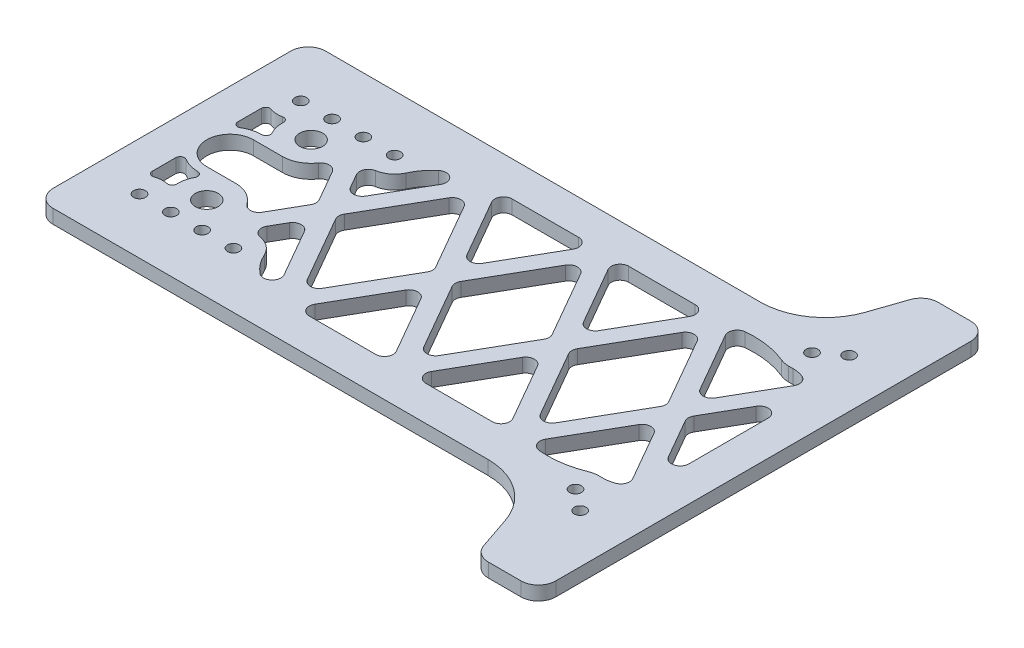
SolidWorks part; units mm, degrees
ref_plane "Front Plane" through (0, 0, 0) normal (0, 0, 1) x (1, 0, 0)
ref_plane "Top Plane" through (0, 0, 0) normal (0, 1, 0) x (1, 0, 0)
ref_plane "Right Plane" through (0, 0, 0) normal (1, 0, 0) x (0, 0, -1)
sketch "Sketch2" plane through (0, 0, 0) normal (0, 1, 0) x (1, 0, 0)
  line L1 (-85, -74.5) -> (85, -74.5)
  line L2 (-85, -74.5) -> (-85, 74.5)
  line L3 (-85, 74.5) -> (85, 74.5)
  line L4 (85, -74.5) -> (85, 74.5)
  line L5 (-85, -74.5) -> (85, 74.5) construction
  line L6 (-85, 74.5) -> (85, -74.5) construction
  point P0 (0, 0)
  dimension "D1" = 149
  dimension "D2" = 170
extrude "Boss-Extrude1" add sketch "Sketch2" along normal blind 4
hole_wizard "M3 Clearance Hole1" positions "Sketch7" profile "Sketch8" hole size "M3" standard "ANSI Metric" end condition through all
sketch "Sketch7" plane through (0, 4, 0) normal (0, 1, 0) x (1, 0, 0)
  line L0 (-85, 74.5) -> (-85, -74.5) construction
  line L1 (-85, -74.5) -> (85, -74.5) construction
  line L2 (85, -74.5) -> (85, 74.5) construction
  point P0 (-71.16, -23.18)
  point P2 (-62.16, -23.18)
  point P4 (-53.16, -23.18)
  point P6 (-44.16, -23.18)
  point P8 (71, -38.66)
  point P10 (65, -34)
  dimension "D1" = 13.84
  dimension "D2" = 51.32
  dimension "D3" = 9
  dimension "D4" = 51.32
  dimension "D5" = 9
  dimension "D6" = 51.32
  dimension "D7" = 9
  dimension "D8" = 51.32
  dimension "D9" = 40.5
  dimension "D10" = 20
  dimension "D11" = 35.84
  dimension "D12" = 14
sketch "Sketch8" plane through (-71.16, 4, 23.18) normal (1, 0, 0) x (0, 0, 1)
  line L0 (0, 0) -> (0, 4)
  line L1 (0, 4) -> (1.7, 4)
  line L2 (1.7, 4) -> (1.7, 0)
  line L5 (1.7, 0) -> (0, 0)
  line L11 (0, -6.35) -> (0, 107.95) construction
  dimension "Thru Hole Dia." = 3.4
  dimension "Thru Hole Depth" = 4
sketch "Sketch9" plane through (0, 4, 0) normal (0, 1, 0) x (1, 0, 0)
  line L0 (-85, 0) -> (85, 0) construction
  line L1 (-85, 74.5) -> (-85, -74.5) construction
  line L2 (85, -74.5) -> (85, 74.5) construction
mirror "Mirror1" about plane through (0, 0, 0) normal (0, 0, 1) of "M3 Clearance Hole1"
sketch "Sketch10" [suppressed] plane through (0, 10, 0) normal (0, 1, 0) x (1, 0, 0)
  line L0 (-85, 74.5) -> (-85, -74.5) construction
  line L1 (-85, -39.5) -> (45.3, -39.5)
  line L2 (-85, -39.5) -> (-85, -74.5)
  line L3 (-85, -74.5) -> (45.3, -74.5)
  line L4 (45.3, -39.5) -> (45.3, -74.5)
  line L5 (-85, -74.5) -> (85, -74.5) construction
  dimension "D1" = 130.3
  dimension "D2" = 35
extrude "Cut-Extrude1" [suppressed] cut sketch "Sketch10" against normal blind 10
sketch "Sketch11" [suppressed] plane through (0, 10, 0) normal (0, 1, 0) x (1, 0, 0)
  line L0 (45.3, -39.5) -> (85, -74.5)
  line L1 (85, -74.5) -> (45.3, -74.5)
  line L2 (45.3, -74.5) -> (45.3, -39.5)
extrude "Cut-Extrude2" [suppressed] cut sketch "Sketch11" against normal blind 10
sketch "Sketch12" plane through (0, 0, 0) normal (0, 1, 0) x (1, 0, 0)
  line L0 (-85, 39.1609) -> (45, 39.1609)
  line L1 (62.6547, 51.8097) -> (67.0194, 64.6606)
  line L2 (67.0194, 64.6606) -> (85, 64.6606)
  line L3 (85, 64.6606) -> (85, 0)
  line L4 (85, -74.5) -> (85, 74.5)
  line L5 (85, 74.5) -> (-85, 74.5)
  line L6 (-85, 74.5) -> (-85, -74.5)
  line L7 (-85, -74.5) -> (85, -74.5)
  line L8 (85, -74.5) -> (85, 74.5)
  line L9 (85, 74.5) -> (-85, 74.5)
  line L10 (-85, 74.5) -> (-85, -74.5)
  line L11 (-85, -74.5) -> (85, -74.5)
  line L12 (-2.2, 0) -> (2.2, 0) construction
  line L13 (67.0194, -64.6606) -> (85, -64.6606)
  line L14 (62.6547, -51.8097) -> (67.0194, -64.6606)
  line L15 (-85, -39.1609) -> (45, -39.1609)
  arc A0 (45, 39.1609) -> (62.6547, 51.8097) centre (45, 57.8061) ccw
  arc A1 (45, -39.1609) -> (62.6547, -51.8097) centre (45, -57.8061) cw
  dimension "D2" = 130
  dimension "D1" = 0
extrude "Cut-Extrude4" cut sketch "Sketch12" against normal through all and the other way through all contours L0 A0 L1 L2 L8 L9 L10 | A1 L15 L10 L11 L8 L13 L14 region at (-8.1008, 0, -57.5262) region at (-8.1008, 0, 57.5262)
hole_wizard "M6 Clearance Hole1" positions "Sketch13" profile "Sketch14" hole size "M6" standard "ANSI Metric" end condition through all
sketch "Sketch13" plane through (0, 4, 0) normal (0, 1, 0) x (1, 0, 0)
  line L0 (-85, 0) -> (85, 0) construction
  line L1 (-2.2, 0) -> (2.2, 0) construction
  line L2 (-85, 39.1609) -> (-85, -39.1609) construction
  point P0 (-60, -15)
  point P8 (-60, 15)
  dimension "D1" = 15
  dimension "D2" = 25
sketch "Sketch14" plane through (-60, 4, 15) normal (1, 0, 0) x (0, 0, 1)
  line L0 (0, 0) -> (0, 4)
  line L1 (0, 4) -> (3.3, 4)
  line L2 (3.3, 4) -> (3.3, 0)
  line L5 (3.3, 0) -> (0, 0)
  line L11 (0, -6.35) -> (0, 107.95) construction
  dimension "Thru Hole Dia." = 6.6
  dimension "Thru Hole Depth" = 4
fillet "Fillet1" radius 5 6 edges at (67.0194, 2, -64.6606) (85, 2, -64.6606) (85, 2, 64.6606) (67.0194, 2, 64.6606) (-85, 2, 39.1609) (-85, 2, -39.1609)
sketch "Sketch15" plane through (0, 4, 0) normal (0, 1, 0) x (1, 0, 0)
  line L0 (65, -27.3) -> (66.2406, -27.3)
  line L1 (-50.31, 17.4014) -> (-23.5629, -29.1609)
  line L2 (-50.31, -17.4014) -> (-23.5629, 29.1609)
  line L3 (-23.5629, -29.1609) -> (9.9394, 29.1609)
  line L4 (9.9394, 29.1609) -> (43.4416, -29.1609)
  line L5 (43.4416, -29.1609) -> (73.5852, 23.3139)
  line L6 (-23.5629, 29.1609) -> (9.9394, -29.1609)
  line L7 (9.9394, -29.1609) -> (43.4416, 29.1609)
  line L8 (43.4416, 29.1609) -> (73.5852, -23.3139)
  line L9 (-2.2, 0) -> (2.2, 0) construction
  line L10 (-60, 6.7) -> (-68.3, 6.7)
  line L11 (-68.3, -6.7) -> (-60, -6.7)
  line L12 (65, 27.3) -> (66.2406, 27.3)
  line L13 (-48.1422, -18.6467) -> (-23.5629, 24.1419)
  line L14 (-23.5629, 24.1419) -> (9.9394, -34.1799)
  line L15 (9.9394, -34.1799) -> (43.4416, 24.1419)
  line L16 (75, 54.6606) -> (74.184, 54.6606)
  line L17 (74.184, 54.6606) -> (72.1234, 48.5937)
  line L18 (45, 29.1609) -> (-75, 29.1609)
  line L19 (-75, 29.1609) -> (-75, -29.1609)
  line L20 (-75, -29.1609) -> (45, -29.1609)
  line L21 (72.1234, -48.5937) -> (74.184, -54.6606)
  line L22 (74.184, -54.6606) -> (75, -54.6606)
  line L23 (75, -54.6606) -> (75, 54.6606)
  line L24 (75, 54.6606) -> (74.184, 54.6606)
  line L25 (74.184, 54.6606) -> (72.1234, 48.5937)
  line L26 (45, 29.1609) -> (-75, 29.1609)
  line L27 (-75, 29.1609) -> (-75, -29.1609)
  line L28 (-75, -29.1609) -> (45, -29.1609)
  line L29 (72.1234, -48.5937) -> (74.184, -54.6606)
  line L30 (74.184, -54.6606) -> (75, -54.6606)
  line L31 (75, -54.6606) -> (75, 54.6606)
  line L32 (43.4416, 24.1419) -> (74.845, -30.5261)
  line L33 (-52.4778, 16.1562) -> (-23.5629, -34.1799)
  line L34 (-23.5629, -34.1799) -> (9.9394, 24.1419)
  line L35 (9.9394, 24.1419) -> (43.4416, -34.1799)
  line L36 (43.4416, -34.1799) -> (75.753, 22.0687)
  line L37 (-52.4778, -16.1562) -> (-23.5629, 34.1799)
  line L38 (-23.5629, 34.1799) -> (9.9394, -24.1419)
  line L39 (9.9394, -24.1419) -> (43.4416, 34.1799)
  line L40 (43.4416, 34.1799) -> (75.753, -22.0687)
  line L41 (-48.1422, 18.6467) -> (-23.5629, -24.1419)
  line L42 (-23.5629, -24.1419) -> (9.9394, 34.1799)
  line L43 (9.9394, 34.1799) -> (43.4416, -24.1419)
  line L44 (43.4416, -24.1419) -> (75, 30.796)
  line L45 (43.4416, -24.1419) -> (71.4174, 24.5592) construction
  line L46 (43.4416, 24.1419) -> (71.4174, -24.5592) construction
  line L47 (-60, 9.2) -> (-68.3, 9.2)
  line L48 (-68.3, -9.2) -> (-60, -9.2)
  arc A0 (66.2406, 27.3) -> (75, 18.5406) centre (66.2406, 18.5406) cw
  circle A1 centre (65, -34) radius 6.7
  arc A2 (66.2406, -27.3) -> (75, -18.5406) centre (66.2406, -18.5406) ccw
  arc A3 (49.055, -29.4493) -> (62.4697, -27.7962) centre (52.7123, -3.8735) ccw
  circle A6 centre (-71.16, -23.18) radius 6.7
  circle A7 centre (-71.16, -23.18) radius 6.7
  circle A11 centre (-71.16, 23.18) radius 6.7
  circle A12 centre (-71.16, 23.18) radius 6.7
  arc A14 (-68.3, 9.2) -> (-77.5, 0) centre (-68.3, 0) ccw
  arc A15 (-77.5, 0) -> (-68.3, -9.2) centre (-68.3, 0) ccw
  arc A16 (45, 29.1609) -> (72.1234, 48.5937) centre (45, 57.8061) ccw
  arc A17 (72.1234, -48.5937) -> (45, -29.1609) centre (45, -57.8061) ccw
  arc A18 (45, 29.1609) -> (72.1234, 48.5937) centre (45, 57.8061) ccw
  arc A19 (72.1234, -48.5937) -> (45, -29.1609) centre (45, -57.8061) ccw
  circle A22 centre (-60, 15) radius 8.3
  circle A23 centre (-60, 15) radius 8.3
  circle A25 centre (-60, -15) radius 8.3
  circle A26 centre (-60, -15) radius 8.3
  circle A28 centre (-44.16, -23.18) radius 6.7
  circle A29 centre (-44.16, -23.18) radius 6.7
  arc A30 (-47.5353, 17.3923) -> (-51.7, 15) centre (-48.9305, 15) ccw
  circle A31 centre (-44.16, 23.18) radius 6.7
  circle A32 centre (-44.16, 23.18) radius 6.7
  arc A33 (-38.0661, 20.3953) -> (-24.4231, 29.1609) centre (-24.4231, 14.1609) cw
  arc A34 (-68.3, 6.7) -> (-75, 0) centre (-68.3, 0) ccw
  arc A35 (-38.0661, -20.3953) -> (-24.4231, -29.1609) centre (-24.4231, -14.1609) ccw
  arc A36 (-47.5353, -17.3923) -> (-51.7, -15) centre (-48.9305, -15) cw
  arc A38 (-75, 0) -> (-68.3, -6.7) centre (-68.3, 0) ccw
  circle A40 centre (71, 38.66) radius 1.7 construction
  circle A41 centre (65, 34) radius 6.7
  circle A42 centre (65, 34) radius 6.7
  circle A43 centre (71, 38.66) radius 1.7
  circle A44 centre (71, 38.66) radius 6.7
  arc A45 (49.055, 29.4493) -> (62.4697, 27.7962) centre (52.7123, 3.8735) cw
  dimension "D6" = 15
  dimension "D1" = 10
  dimension "D2" = 5
  dimension "D3" = 5
  dimension "D4" = 5
  dimension "D5" = 5
  dimension "D7" = 5
  dimension "D8" = 5
  dimension "D9" = 2.5
  dimension "D10" = 2.5
  dimension "D11" = 5
  dimension "D12" = 5
  dimension "D13" = 2.5
extrude "Cut-Extrude5" cut sketch "Sketch15" against normal blind 10 contours A34 A38 L11 A26 L37 L33 A23 L10 | A29 A35 L33 L13 | A33 A32 L41 L37 | L41 L42 L14 L13 | L38 L42 L26 | L34 L28 L14 | L38 L39 L35 L34 | L35 L15 L28 | L26 L43 L39 | L43 L44 L32 L15 | A19 A3 A1 L0 A2 L8 L36 | L40 A2 L31 A0 L36 | A45 A18 L40 L5 A0 L12 A42 | A26 L48 A15 L27 A7 | A23 A12 L27 A14 L47 region at (59.4111, 4, 20.6055) region at (71.0202, 4, 0) region at (43.4416, 4, 0) region at (26.6905, 4, 21.1136) region at (59.4111, 4, -20.6055) region at (26.6905, 4, -21.1136) region at (-6.8117, 4, 21.1136) region at (9.9394, 4, 0) region at (-6.8117, 4, -21.1136) region at (-23.5629, 4, 0) region at (-37.1278, 4, 17.2387) region at (-37.1278, 4, -17.2387) region at (-58.202, 4, 0) region at (-71.5587, 4, -12.3944) region at (-71.5587, 4, 12.3944)
fillet "Fillet2" radius 2.5 42 edges at (7.0563, 2, 29.1609) (-20.6797, 2, 29.1609) (-6.8117, 2, 5.019) (12.8225, 2, 29.1609) (26.6905, 2, 5.019) (40.5585, 2, 29.1609) (-40.314, 2, 5.019) (-26.5315, 2, 29.012) (-47.3672, 2, 17.2975) (-40.314, 2, -5.019) (-47.3672, 2, -17.2975) (-26.5315, 2, -29.012) (71.8329, 2, -25.2825) (60.1927, 2, -5.019) (46.3076, 2, -29.1907) (60.1927, 2, 5.019) (71.8329, 2, 25.2825) (46.3076, 2, 29.1907) (-51.7023, 2, -14.8061) (-43.1971, 2, 0) (-51.7023, 2, 14.8061) (29.5736, 2, 0) (43.4416, 2, -24.1419) (57.3096, 2, 0) (43.4416, 2, 24.1419) (63.0759, 2, 0) (74.7987, 2, -20.4075) (74.7987, 2, 20.4075) (-37.4309, 2, 0) (-23.5629, 2, -24.1419) (-9.6949, 2, 0) (-23.5629, 2, 24.1419) (7.0563, 2, -29.1609) (-6.8117, 2, -5.019) (40.5585, 2, -29.1609) (26.6905, 2, -5.019) (12.8225, 2, -29.1609) (-3.9286, 2, 0) (9.9394, 2, -24.1419) (23.8074, 2, 0) (9.9394, 2, 24.1419) (-20.6797, 2, -29.1609)
fillet "Fillet3" radius 1.25 8 edges at (-75, 2, 17.6896) (-65.9372, 2, 9.2) (-67.9799, 2, 17.2828) (-75, 2, -6.3048) (-75, 2, -17.6896) (-67.9799, 2, -17.2828) (-65.9372, 2, -9.2) (-75, 2, 6.3048)
